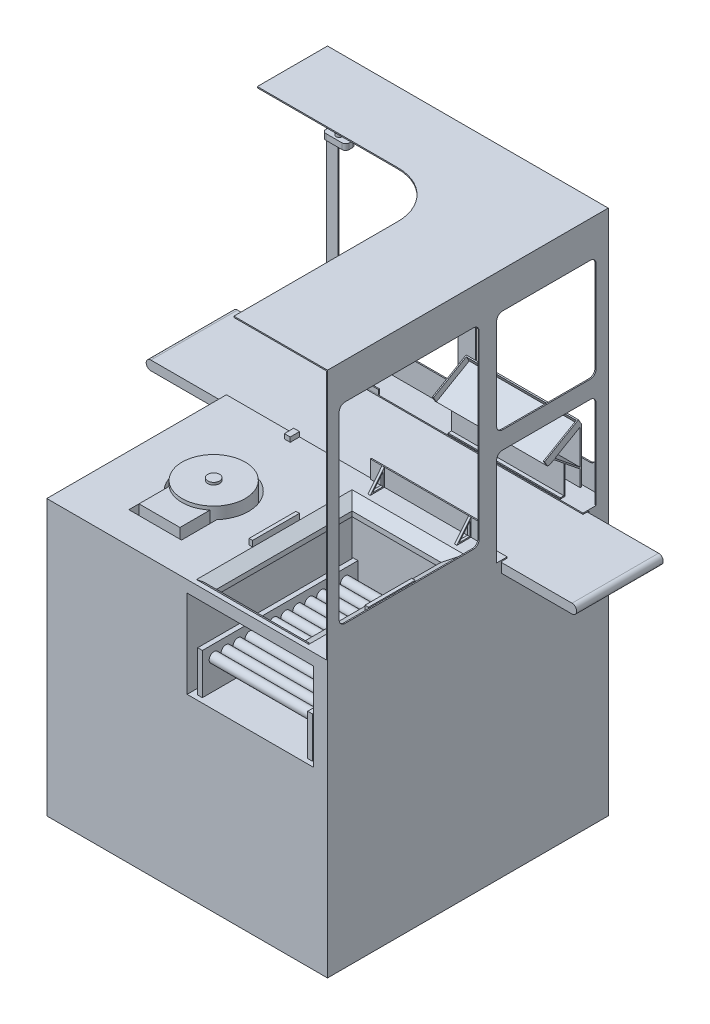
SolidWorks part; units mm, degrees
ref_plane "Front Plane" through (0, 0, 0) normal (0, 0, 1) x (1, 0, 0)
ref_plane "Top Plane" through (0, 0, 0) normal (0, 1, 0) x (1, 0, 0)
ref_plane "Right Plane" through (0, 0, 0) normal (1, 0, 0) x (0, 0, -1)
sketch "Sketch1" plane through (0, 0, 0) normal (0, 1, 0) x (1, 0, 0)
  line L0 (-595, 595) -> (595, 595)
  line L1 (-600, 600) -> (600, 600)
  line L2 (-600, 600) -> (-600, -600)
  line L3 (-600, -600) -> (600, -600)
  line L4 (600, 600) -> (600, -600)
  line L5 (595, 595) -> (595, -595)
  line L6 (-595, -595) -> (595, -595)
  line L7 (-595, 595) -> (-595, -595)
  dimension "D1" = 1200
  dimension "D2" = 1200
  dimension "D3" = 600
  dimension "D4" = 600
  dimension "D5" = 5
extrude "Boss-Extrude1" add sketch "Sketch1" along normal blind 1125 contours L0 L5 L6 L7 | L2 L1 L4 L3
sketch "Sketch2" plane through (0, 0, 600) normal (0, 0, 1) x (1, 0, 0)
  line L0 (-600, 1125) -> (600, 1125) construction
  line L1 (540, 1125) -> (0, 1125)
  line L2 (540, 1125) -> (540, 750)
  line L3 (540, 750) -> (0, 750)
  line L4 (0, 1125) -> (0, 750)
  line L5 (600, 1125) -> (600, 0) construction
  dimension "D1" = 540
  dimension "D2" = 600
  dimension "D3" = 375
extrude "Cut-Extrude1" cut sketch "Sketch2" against normal blind 50
sketch "Sketch3" plane through (0, 0, -595) normal (0, 0, 1) x (1, 0, 0)
  line L0 (-900, 1125) -> (900, 1125)
  line L1 (900, 1165) -> (-900, 1165)
  line L2 (-600, 1125) -> (0, 1125) construction
  arc A0 (-900, 1125) -> (-900, 1165) centre (-900, 1145) cw
  arc A1 (900, 1125) -> (900, 1165) centre (900, 1145) ccw
  dimension "D1" = 1800
  dimension "D2" = 900
  dimension "D3" = 40
  dimension "D4" = 0
extrude "Boss-Extrude2" add sketch "Sketch3" along normal blind 370 from offset 80 separate body
sketch "Sketch4" plane through (0, 1125, 0) normal (0, 1, 0) x (1, 0, 0)
  line L0 (600, 600) -> (600, -600) construction
  line L1 (-600, -600) -> (600, -600)
  line L2 (-600, -600) -> (-600, 143)
  line L3 (-600, 143) -> (600, 143)
  line L4 (600, -600) -> (600, 143)
  line L5 (900, 145) -> (-900, 145) construction
  line L6 (900, 515) -> (-900, 515) construction
  line L7 (-600, 600) -> (600, 600)
  line L8 (-600, 600) -> (-600, 517)
  line L9 (-600, 517) -> (600, 517)
  line L10 (600, 600) -> (600, 517)
  dimension "D1" = 2
  dimension "D2" = 2
extrude "Boss-Extrude3" add sketch "Sketch4" along normal blind 50
sketch "Sketch5" plane through (0, 1175, 0) normal (0, 1, 0) x (1, 0, 0)
  line L0 (-600, -600) -> (600, -600) construction
  line L1 (70, -565) -> (450, -565)
  line L2 (70, -565) -> (70, 35)
  line L3 (70, 35) -> (450, 35)
  line L4 (450, -565) -> (450, 35)
  line L5 (600, -600) -> (600, 143) construction
  dimension "D1" = 35
  dimension "D2" = 150
  dimension "D3" = 380
  dimension "D4" = 600
extrude "Cut-Extrude2" cut sketch "Sketch5" against normal blind 50
sketch "Sketch6" plane through (0, 1125, 0) normal (0, -1, 0) x (1, 0, 0)
  line L0 (0, 595) -> (0, -105)
  line L1 (540, 595) -> (540, -105)
  line L2 (540, -105) -> (0, -105)
  line L3 (-595, 595) -> (0, 595) construction
  line L4 (0, 595) -> (-5, 595)
  line L5 (-5, 595) -> (-5, -110)
  line L6 (-5, -110) -> (545, -110)
  line L7 (545, -110) -> (545, 595)
  line L8 (540, 595) -> (595, 595) construction
  line L9 (545, 595) -> (540, 595)
  line L11 (450, -35) -> (70, -35) construction
  dimension "D1" = 5
  dimension "D2" = 5
  dimension "D3" = 5
  dimension "D4" = 70
extrude "Boss-Extrude4" add sketch "Sketch6" along normal up to surface (375 mm away) up to face at (270, 750, 597.5)
sketch "Sketch7" plane through (0, 750, 0) normal (0, -1, 0) x (1, 0, 0)
  line L1 (-5, -110) -> (545, -110)
  line L2 (-5, -110) -> (-5, 595)
  line L3 (-5, 595) -> (545, 595)
  line L4 (545, -110) -> (545, 595)
extrude "Boss-Extrude5" add sketch "Sketch7" along normal blind 5
chamfer "Chamfer1" distance 50 angle 30 3 edges at (70, 1175, 265) (450, 1175, 265) (260, 1175, -35) first distance on face at (260, 1175, 265)
chamfer "Chamfer2" distance 15 angle 30 1 edges at (260, 1175, 565) first distance on face at (260, 1175, 240)
sketch "Sketch8" plane through (0, 0, -517) normal (0, 0, 1) x (1, 0, 0)
  line L0 (600, 1175) -> (600, 1125) construction
  line L1 (-600, 1175) -> (600, 1175)
  line L2 (-600, 1175) -> (-600, 1170)
  line L3 (-600, 1170) -> (600, 1170)
  line L4 (600, 1175) -> (600, 1170)
  dimension "D1" = 5
extrude "Boss-Extrude6" add sketch "Sketch8" along normal blind 25
sketch "Sketch9" plane through (0, 0, -143) normal (0, 0, -1) x (-1, 0, 0)
  line L0 (600, 1175) -> (600, 1125) construction
  line L1 (-600, 1175) -> (600, 1175)
  line L2 (-600, 1175) -> (-600, 1170)
  line L3 (-600, 1170) -> (600, 1170)
  line L4 (600, 1175) -> (600, 1170)
  dimension "D1" = 5
extrude "Boss-Extrude7" add sketch "Sketch9" along normal blind 25
sketch "Sketch10" plane through (0, 750, 0) normal (0, 1, 0) x (1, 0, 0)
  line L0 (0, 105) -> (0, -600) construction
  line L1 (25, -580) -> (45, -580)
  line L2 (25, -580) -> (25, 85)
  line L3 (25, 85) -> (45, 85)
  line L4 (45, -580) -> (45, 85)
  line L5 (495, 85) -> (515, 85)
  line L6 (495, 85) -> (495, -580)
  line L7 (495, -580) -> (515, -580)
  line L8 (515, 85) -> (515, -580)
  line L9 (540, 105) -> (540, -600) construction
  line L10 (0, -600) -> (540, -600) construction
  line L11 (540, 105) -> (0, 105) construction
  dimension "D1" = 25
  dimension "D2" = 25
  dimension "D3" = 20
  dimension "D4" = 20
  dimension "D5" = 20
  dimension "D6" = 20
  dimension "D7" = 20
  dimension "D8" = 20
extrude "Boss-Extrude8" add sketch "Sketch10" along normal blind 175
sketch "Sketch11" plane through (45, 0, 0) normal (1, 0, 0) x (0, 0, -1)
  line L0 (-580, 925) -> (85, 925) construction
  line L1 (-580, 925) -> (-580, 750) construction
  circle A0 centre (-530, 875) radius 20.8316
  circle A1 centre (-479, 875) radius 20.8316
  circle A2 centre (-428, 875) radius 20.8316
  circle A3 centre (-377, 875) radius 20.8316
  circle A4 centre (-326, 875) radius 20.8316
  circle A5 centre (-275, 875) radius 20.8316
  circle A6 centre (-224, 875) radius 20.8316
  circle A7 centre (-173, 875) radius 20.8316
  circle A8 centre (-122, 875) radius 20.8316
  circle A9 centre (-71, 875) radius 20.8316
  circle A10 centre (-20, 875) radius 20.8316
  circle A11 centre (31, 875) radius 20.8316
  dimension "D1" = 50
  dimension "D2" = 50
  dimension "D3" = 12
extrude "Boss-Extrude9" add sketch "Sketch11" along normal up to surface (450 mm away) up to face at (495, 837.5, 247.5)
sketch "Sketch12" plane through (0, 1175, 0) normal (0, 1, 0) x (1, 0, 0)
  line L0 (600, 492) -> (600, 600) construction
  line L1 (-600, 600) -> (600, 600)
  line L2 (-600, 600) -> (-600, 595)
  line L3 (-600, 595) -> (600, 595)
  line L4 (600, 600) -> (600, 595)
  dimension "D1" = 5
extrude "Boss-Extrude10" add sketch "Sketch12" along normal blind 1070
sketch "Sketch13" plane through (0, 0, -595) normal (0, 0, 1) x (1, 0, 0)
  line L0 (-600, 2245) -> (-600, 1175) construction
  line L1 (-525, 2095) -> (-62.5, 2095)
  line L2 (-550, 2070) -> (-550, 1300)
  line L3 (-525, 1275) -> (-62.5, 1275)
  line L4 (-37.5, 2070) -> (-37.5, 1300)
  line L5 (62.5, 2095) -> (525, 2095)
  line L6 (37.5, 2070) -> (37.5, 1300)
  line L7 (62.5, 1275) -> (525, 1275)
  line L8 (550, 2070) -> (550, 1300)
  line L9 (600, 2245) -> (600, 1175) construction
  line L10 (-600, 1175) -> (600, 1175) construction
  line L11 (-600, 2245) -> (600, 2245) construction
  arc A0 (37.5, 2070) -> (62.5, 2095) centre (62.5, 2070) cw
  arc A1 (550, 2070) -> (525, 2095) centre (525, 2070) ccw
  arc A2 (525, 1275) -> (550, 1300) centre (525, 1300) ccw
  arc A3 (62.5, 1275) -> (37.5, 1300) centre (62.5, 1300) cw
  arc A4 (-525, 1275) -> (-550, 1300) centre (-525, 1300) cw
  arc A5 (-37.5, 1300) -> (-62.5, 1275) centre (-62.5, 1300) cw
  arc A6 (-62.5, 2095) -> (-37.5, 2070) centre (-62.5, 2070) cw
  arc A7 (-525, 2095) -> (-550, 2070) centre (-525, 2070) ccw
  dimension "D9" = 25
  dimension "D1" = 50
  dimension "D2" = 50
  dimension "D3" = 75
  dimension "D4" = 100
  dimension "D5" = 100
  dimension "D6" = 150
  dimension "D7" = 150
  dimension "D8" = 562.5
extrude "Cut-Extrude3" cut sketch "Sketch13" against normal blind 50
sketch "Sketch14" plane through (0, 1175, 0) normal (0, 1, 0) x (1, 0, 0)
  line L0 (-600, -600) -> (600, -600) construction
  line L1 (600, 595) -> (595, 595)
  line L2 (600, 595) -> (600, -600)
  line L3 (600, -600) -> (595, -600)
  line L4 (595, 595) -> (595, -600)
  dimension "D1" = 5
extrude "Boss-Extrude11" add sketch "Sketch14" along normal up to surface (1070 mm away) up to face at (0, 2245, -597.5)
sketch "Sketch15" plane through (595, 0, 0) normal (-1, 0, 0) x (0, 0, 1)
  line L0 (-595, 1175) -> (-492, 1175) construction
  line L1 (-548, 1175) -> (-123, 1175)
  line L2 (-548, 1175) -> (-548, 1555)
  line L3 (-523, 1580) -> (-148, 1580)
  line L4 (-123, 1175) -> (-123, 1555)
  line L5 (-595, 2245) -> (-595, 1175) construction
  line L6 (-168, 1175) -> (600, 1175) construction
  line L7 (-523, 1655) -> (-148, 1655)
  line L8 (-548, 1680) -> (-548, 2070)
  line L9 (-523, 2095) -> (-148, 2095)
  line L10 (-123, 1680) -> (-123, 2070)
  line L11 (-23, 2095) -> (525, 2095)
  line L12 (-48, 2070) -> (-48, 1300)
  line L13 (-23, 1275) -> (525, 1275)
  line L14 (550, 2070) -> (550, 1300)
  line L15 (-595, 2245) -> (600, 2245) construction
  line L16 (600, 2245) -> (600, 1175) construction
  arc A0 (-523, 1580) -> (-548, 1555) centre (-523, 1555) ccw
  arc A1 (-148, 1580) -> (-123, 1555) centre (-148, 1555) cw
  arc A2 (550, 1300) -> (525, 1275) centre (525, 1300) cw
  arc A3 (-23, 1275) -> (-48, 1300) centre (-23, 1300) cw
  arc A4 (550, 2070) -> (525, 2095) centre (525, 2070) ccw
  arc A5 (-23, 2095) -> (-48, 2070) centre (-23, 2070) ccw
  arc A6 (-523, 1655) -> (-548, 1680) centre (-523, 1680) cw
  arc A7 (-123, 1680) -> (-148, 1655) centre (-148, 1680) cw
  arc A8 (-123, 2070) -> (-148, 2095) centre (-148, 2070) ccw
  arc A9 (-523, 2095) -> (-548, 2070) centre (-523, 2070) ccw
  point P24 (-548, 1580)
  point P41 (-123, 2095)
  point P44 (-548, 2095)
  dimension "D12" = 25
  dimension "D1" = 425
  dimension "D2" = 47
  dimension "D3" = 100
  dimension "D4" = 150
  dimension "D5" = 150
  dimension "D6" = 75
  dimension "D7" = 47
  dimension "D8" = 75
  dimension "D9" = 425
  dimension "D10" = 405
  dimension "D11" = 50
extrude "Cut-Extrude4" cut sketch "Sketch15" against normal blind 50
sketch "Sketch25" plane through (0, 2245, 0) normal (0, 1, 0) x (1, 0, 0)
  line L0 (-600, 600) -> (-600, 300)
  line L1 (-600, 300) -> (0, 300)
  line L2 (-600, 600) -> (600, 600)
  line L3 (600, 600) -> (600, -600)
  line L4 (600, -600) -> (200, -600)
  line L5 (-600, -600) -> (595, -600) construction
  line L6 (200, -600) -> (200, 100)
  arc A0 (0, 300) -> (200, 100) centre (0, 100) cw
  dimension "D1" = 400
  dimension "D2" = 300
  dimension "D3" = 600
  dimension "D4" = 700
extrude "Boss-Extrude14" add sketch "Sketch25" along normal blind 5
sketch "Sketch26" plane through (0, 1175, 0) normal (0, 1, 0) x (1, 0, 0)
  line L0 (600, 492) -> (-600, 492) construction
  line L1 (-325, 492) -> (-275, 492)
  line L2 (-325, 492) -> (-325, 497)
  line L3 (-325, 497) -> (-275, 497)
  line L4 (-275, 492) -> (-275, 497)
  line L5 (-600, 168) -> (600, 168) construction
  line L6 (-312.5, 168) -> (-287.5, 168)
  line L7 (-312.5, 168) -> (-312.5, 128)
  line L8 (-312.5, 128) -> (-287.5, 128)
  line L9 (-287.5, 168) -> (-287.5, 128)
  line L10 (-600, 595) -> (-600, 492) construction
  line L11 (-600, 168) -> (-600, -600) construction
  dimension "D1" = 5
  dimension "D2" = 50
  dimension "D3" = 275
  dimension "D4" = 25
  dimension "D5" = 40
  dimension "D6" = 287.5
extrude "Boss-Extrude15" add sketch "Sketch26" along normal blind 20 separate body
sketch "Sketch28" plane through (0, 2245, 0) normal (0, -1, 0) x (1, 0, 0)
  line L0 (-600, -595) -> (-600, -300) construction
  line L1 (-600, -595) -> (595, -595) construction
  circle A0 centre (-300, -350) radius 12.5
  dimension "D2" = 25
  dimension "D1" = 300
  dimension "D3" = 245
extrude "Boss-Extrude16" add sketch "Sketch28" along normal blind 50 separate body
sketch "Sketch29" plane through (0, 2195, 0) normal (0, -1, 0) x (1, 0, 0)
  line L1 (-335, -327.5) -> (-265, -327.5)
  line L2 (-350, -342.5) -> (-350, -357.5)
  line L3 (-335, -372.5) -> (-265, -372.5)
  line L4 (-250, -342.5) -> (-250, -357.5)
  circle A0 centre (-300, -350) radius 12.5 construction
  arc A1 (-250, -342.5) -> (-265, -327.5) centre (-265, -342.5) ccw
  arc A2 (-265, -372.5) -> (-250, -357.5) centre (-265, -357.5) ccw
  arc A3 (-335, -372.5) -> (-350, -357.5) centre (-335, -357.5) cw
  arc A4 (-335, -327.5) -> (-350, -342.5) centre (-335, -342.5) ccw
  point P8 (-250, -327.5)
  point P11 (-250, -372.5)
  point P16 (-350, -327.5)
  dimension "D3" = 22.5
  dimension "D5" = 15
  dimension "D1" = 100
  dimension "D2" = 45
  dimension "D4" = 50
extrude "Boss-Extrude17" add sketch "Sketch29" along normal blind 25 contours A4 L2 A3 L3 A2 L4 A1 L1
sketch "Sketch30" plane through (0, 2245, 0) normal (0, -1, 0) x (1, 0, 0)
  line L0 (200, 600) -> (595, 600) construction
  line L2 (595, -595) -> (595, 600) construction
  circle A0 centre (273, 250) radius 12.5
  dimension "D2" = 322
  dimension "D3" = 25
  dimension "D1" = 350
extrude "Boss-Extrude18" add sketch "Sketch30" along normal blind 50 separate body
sketch "Sketch32" plane through (0, 2195, 0) normal (0, -1, 0) x (1, 0, 0)
  line L1 (265.5, 300) -> (280.5, 300)
  line L2 (250.5, 285) -> (250.5, 215)
  line L3 (265.5, 200) -> (280.5, 200)
  line L4 (295.5, 285) -> (295.5, 215)
  circle A0 centre (273, 250) radius 12.5 construction
  arc A1 (295.5, 215) -> (280.5, 200) centre (280.5, 215) cw
  arc A2 (265.5, 200) -> (250.5, 215) centre (265.5, 215) cw
  arc A3 (280.5, 300) -> (295.5, 285) centre (280.5, 285) cw
  arc A4 (265.5, 300) -> (250.5, 285) centre (265.5, 285) ccw
  point P10 (250.5, 200)
  point P13 (295.5, 300)
  point P16 (250.5, 300)
  dimension "D5" = 15
  dimension "D1" = 100
  dimension "D2" = 45
  dimension "D3" = 50
  dimension "D4" = 22.5
extrude "Boss-Extrude19" add sketch "Sketch32" along normal blind 25
sketch "Sketch33" plane through (0, 1175, 0) normal (0, 1, 0) x (1, 0, 0)
  line L0 (500, 85) -> (500, -580) construction
  line L1 (500, -140) -> (515, -140)
  line L2 (500, -140) -> (500, -340)
  line L3 (500, -340) -> (515, -340)
  line L4 (515, -140) -> (515, -340)
  line L5 (20, -580) -> (20, 85) construction
  line L6 (20, -140) -> (5, -140)
  line L7 (20, -140) -> (20, -340)
  line L8 (20, -340) -> (5, -340)
  line L9 (5, -140) -> (5, -340)
  line L10 (20, 85) -> (500, 85) construction
  dimension "D1" = 15
  dimension "D2" = 15
  dimension "D3" = 200
  dimension "D4" = 200
  dimension "D5" = 225
  dimension "D6" = 225
extrude "Boss-Extrude20" add sketch "Sketch33" along normal blind 25 separate body
sketch "Sketch34" plane through (0, 1175, 0) normal (0, 1, 0) x (1, 0, 0)
  line L0 (-600, -600) -> (595, -600) construction
  line L1 (-383.1327, -216) -> (-158.1327, -216)
  line L2 (-383.1327, -216) -> (-383.1327, -466)
  line L3 (-383.1327, -466) -> (-158.1327, -466)
  line L4 (-158.1327, -216) -> (-158.1327, -466)
  circle A0 centre (-270.6327, -216) radius 150
  dimension "D1" = 300
  dimension "D2" = 384
  dimension "D3" = 225
  dimension "D4" = 250
extrude "Cut-Extrude6" cut sketch "Sketch34" against normal blind 50 contours L4 A0 L2 L1 | L2 A0 L4 L1 | A0 L2 L3 L4 region at (-270.6327, 1175, 165.1468) region at (-270.6327, 1175, 284.0035) region at (-270.6327, 1175, 407.2808)
sketch "Sketch35" plane through (0, 1125, 0) normal (0, -1, 0) x (1, 0, 0)
  line L0 (-383.1327, 466) -> (-158.1327, 466)
  line L1 (-158.1327, 466) -> (-158.1327, 315.2157)
  line L2 (-383.1327, 466) -> (-383.1327, 315.2157)
  line L3 (-153.1327, 471) -> (-153.1327, 317.0878)
  line L4 (-388.1327, 471) -> (-153.1327, 471)
  line L5 (-388.1327, 471) -> (-388.1327, 317.0878)
  arc A1 (-383.1327, 315.2157) -> (-158.1327, 315.2157) centre (-270.6327, 216) ccw
  arc A2 (-388.1327, 317.0878) -> (-153.1327, 317.0878) centre (-270.6327, 216) ccw
  dimension "D1" = 5
extrude "Boss-Extrude21" add sketch "Sketch35" along normal blind 50
sketch "Sketch36" plane through (0, 1075, 0) normal (0, -1, 0) x (1, 0, 0)
  line L0 (-388.1327, 471) -> (-388.1327, 317.0878)
  line L1 (-388.1327, 471) -> (-153.1327, 471)
  line L2 (-153.1327, 471) -> (-153.1327, 317.0878)
  arc A0 (-153.1327, 317.0878) -> (-388.1327, 317.0878) centre (-270.6327, 216) cw
extrude "Boss-Extrude22" add sketch "Sketch36" along normal blind 5
sketch "Sketch37" plane through (0, 1075, 0) normal (0, 1, 0) x (1, 0, 0)
  circle A0 centre (-270.6327, -216) radius 135
  dimension "D1" = 270
extrude "Boss-Extrude23" add sketch "Sketch37" along normal blind 140
sketch "Sketch38" plane through (0, 1075, 0) normal (0, 1, 0) x (1, 0, 0)
  line L0 (-358.1327, -447.5778) -> (-183.1327, -447.5778)
  line L1 (-183.1327, -447.5778) -> (-183.1327, -318.8044)
  line L2 (-358.1327, -447.5778) -> (-358.1327, -318.8044)
  line L3 (-383.1327, -466) -> (-383.1327, -315.2157) construction
  circle A0 centre (-270.6327, -216) radius 135 construction
  arc A1 (-358.1327, -318.8044) -> (-183.1327, -318.8044) centre (-270.6327, -216) ccw
  dimension "D1" = 175
  dimension "D2" = 25
extrude "Boss-Extrude24" add sketch "Sketch38" along normal blind 125
sketch "Sketch39" plane through (0, 1215, 0) normal (0, 1, 0) x (1, 0, 0)
  circle A1 centre (-270.6327, -216) radius 25
  dimension "D1" = 50
extrude "Boss-Extrude25" add sketch "Sketch39" along normal blind 10
sketch "Sketch40" plane through (0, 1175, 0) normal (0, 1, 0) x (1, 0, 0)
  line L0 (-600, 168) -> (600, 168) construction
  line L1 (20, 168) -> (500, 168)
  line L2 (20, 168) -> (20, 163)
  line L3 (20, 163) -> (500, 163)
  line L4 (500, 168) -> (500, 163)
  line L5 (500, 85) -> (500, -580) construction
  line L6 (20, -580) -> (20, 85) construction
  dimension "D1" = 0
  dimension "D2" = 0
  dimension "D3" = 5
extrude "Boss-Extrude26" add sketch "Sketch40" along normal blind 75
sketch "Sketch41" plane through (20, 0, 0) normal (-1, 0, 0) x (0, 0, 1)
  line L0 (-163, 1175) -> (-103, 1175)
  line L1 (-103, 1175) -> (-163, 1250)
  line L2 (-163, 1250) -> (-163, 1175)
  line L3 (-113.4031, 1180) -> (-158, 1235.7461)
  line L4 (-158, 1235.7461) -> (-158, 1180)
  line L5 (-158, 1180) -> (-113.4031, 1180)
  dimension "D2" = 60
  dimension "D1" = 5
extrude "Boss-Extrude27" add sketch "Sketch41" against normal blind 10 from offset 50 offset against normal yes
sketch "Sketch42" plane through (500, 0, 0) normal (1, 0, 0) x (0, 0, -1)
  line L0 (163, 1175) -> (103, 1175)
  line L1 (103, 1175) -> (163, 1250)
  line L2 (163, 1250) -> (163, 1175)
  line L3 (113.4031, 1180) -> (158, 1235.7461)
  line L4 (158, 1235.7461) -> (158, 1180)
  line L5 (158, 1180) -> (113.4031, 1180)
  dimension "D1" = 60
  dimension "D2" = 5
extrude "Boss-Extrude28" add sketch "Sketch42" against normal blind 10 from offset 50 offset against normal yes
sketch "Sketch44" plane through (0, 1175, 0) normal (0, 1, 0) x (1, 0, 0)
  line L0 (20, 168) -> (20, 163) construction
  line L1 (20, 585) -> (500, 585)
  line L2 (20, 585) -> (20, 580)
  line L3 (20, 580) -> (500, 580)
  line L4 (500, 585) -> (500, 580)
  line L5 (500, 163) -> (500, 168) construction
  line L6 (-600, 595) -> (595, 595) construction
  dimension "D1" = 0
  dimension "D2" = 0
  dimension "D3" = 10
  dimension "D4" = 5
extrude "Boss-Extrude30" add sketch "Sketch44" along normal blind 300
sketch "Sketch45" plane through (0, 0, -580) normal (0, 0, 1) x (1, 0, 0)
  line L0 (500, 1475) -> (500, 1175) construction
  line L1 (20, 1475) -> (500, 1475)
  line L2 (20, 1475) -> (20, 1325)
  line L3 (20, 1325) -> (500, 1325)
  line L4 (500, 1475) -> (500, 1325)
  line L6 (20, 1175) -> (500, 1175) construction
  dimension "D1" = 150
extrude "Boss-Extrude31" add sketch "Sketch45" along normal blind 225
sketch "Sketch46" plane through (20, 0, 0) normal (-1, 0, 0) x (0, 0, 1)
  line L0 (-580, 1325) -> (-580, 1400)
  line L7 (-580, 1400) -> (-450.0962, 1325)
  line L8 (-355, 1325) -> (-580, 1325) construction
  line L9 (-450.0962, 1325) -> (-580, 1325)
  line L15 (-585, 1475) -> (-355, 1475) construction
  line L16 (-581.3002, 1406.5242) -> (-440.0962, 1325)
  line L17 (-440.0962, 1325) -> (-355, 1325)
  line L18 (-355, 1325) -> (-355, 1475)
  line L19 (-355, 1475) -> (-580, 1475)
  line L20 (-581.3002, 1406.5242) -> (-585, 1408.6603)
  line L21 (-585, 1475) -> (-585, 1175) construction
  line L22 (-585, 1408.6603) -> (-585, 1475)
  line L23 (-585, 1475) -> (-580, 1475)
  dimension "D1" = 60
  dimension "D2" = 75
  dimension "D3" = 5
extrude "Cut-Extrude7" cut sketch "Sketch46" against normal blind 550
sketch "Sketch47" plane through (0, 1175, 0) normal (0, 1, 0) x (1, 0, 0)
  line L0 (500, 580) -> (500, 585) construction
  line L1 (20, 580) -> (500, 580)
  line L2 (20, 580) -> (20, 440.0962)
  line L3 (20, 440.0962) -> (500, 440.0962)
  line L4 (500, 580) -> (500, 440.0962)
  line L5 (500, 440.0962) -> (20, 440.0962) construction
  dimension "D1" = 0
  dimension "D2" = 0
extrude "Boss-Extrude32" add sketch "Sketch47" along normal up to surface (225 mm away) up to face at (260, 1362.5, -515.0481)
sketch "Sketch48" plane through (20, 0, 0) normal (-1, 0, 0) x (0, 0, 1)
  line L0 (-450.0962, 1325) -> (-580, 1400)
  line L2 (-580, 1400) -> (-580, 1175)
  line L3 (-585, 1175) -> (-492, 1175) construction
  line L4 (-467.551, 1335.0775) -> (-580, 1244.1351)
  line L5 (-472.1903, 1337.756) -> (-580, 1250.5656)
  line L6 (-510.3401, 1175) -> (-510.3401, 1300.4721)
  line L7 (-515.3401, 1296.4284) -> (-515.3401, 1175)
  line L8 (-585, 1408.6603) -> (-585, 1175) construction
  line L9 (-585, 1408.6603) -> (-440.0962, 1325) construction
  line L10 (-450.0962, 1325) -> (-440.0962, 1319.2265)
  line L11 (-440.0962, 1319.2265) -> (-440.0962, 1175)
  line L12 (-440.0962, 1175) -> (-510.3401, 1175)
  line L13 (-580, 1175) -> (-515.3401, 1175)
  line L14 (-580, 1250.5656) -> (-580, 1400)
  line M5 (-585, 1175) -> (-492, 1175)
  line M6 (-492, 1175) -> (-440.0962, 1175)
  line M7 (-440.0962, 1175) -> (-440.0962, 1319.2265)
  line M11 (-440.0962, 1319.2265) -> (-450.0962, 1325)
  dimension "D1" = 5
  dimension "D2" = 5
  dimension "D3" = 5
  dimension "D4" = 180
extrude "Cut-Extrude8" cut sketch "Sketch48" against normal blind 550 contours L5 L0 L2 | L6 L0 L4 M5 M6 M7 M11 | L7 L4 L2 M5 region at (20, 1248.5269, -474.2662) region at (20, 1329.4406, -544.0634) region at (20, 1223.8367, -544.7128)
sketch "Sketch49" plane through (0, 803.1828, 463.7178) normal (0, 0.866, 0.5) x (1, 0, 0)
  line L0 (500, 1210.955) -> (20, 1210.955) construction
  line L1 (20, 1043.6345) -> (25, 1043.6345)
  line L2 (20, 1043.6345) -> (20, 1210.955)
  line L3 (20, 1210.955) -> (25, 1210.955)
  line L5 (500, 1043.6345) -> (20, 1043.6345) construction
  line L6 (500, 1210.955) -> (495, 1210.955)
  line L7 (500, 1210.955) -> (500, 1043.6345)
  line L8 (500, 1043.6345) -> (495, 1043.6345)
  line L10 (25, 1205.955) -> (25, 1043.6345)
  line L11 (495, 1210.955) -> (25, 1210.955)
  line L13 (495, 1205.955) -> (25, 1205.955)
  line L15 (495, 1205.955) -> (495, 1043.6345)
  dimension "D1" = 5
  dimension "D2" = 5
  dimension "D3" = 5
extrude "Boss-Extrude33" add sketch "Sketch49" along normal blind 25
sketch "Sketch50" plane through (0, 0, -510.3401) normal (0, 0, 1) x (1, 0, 0)
  line L0 (500, 1175) -> (500, 1300.4721) construction
  line L1 (20, 1175) -> (500, 1175)
  line L2 (20, 1175) -> (20, 1180)
  line L3 (20, 1180) -> (500, 1180)
  line L4 (500, 1175) -> (500, 1180)
  dimension "D1" = 5
extrude "Boss-Extrude34" add sketch "Sketch50" along normal blind 15
